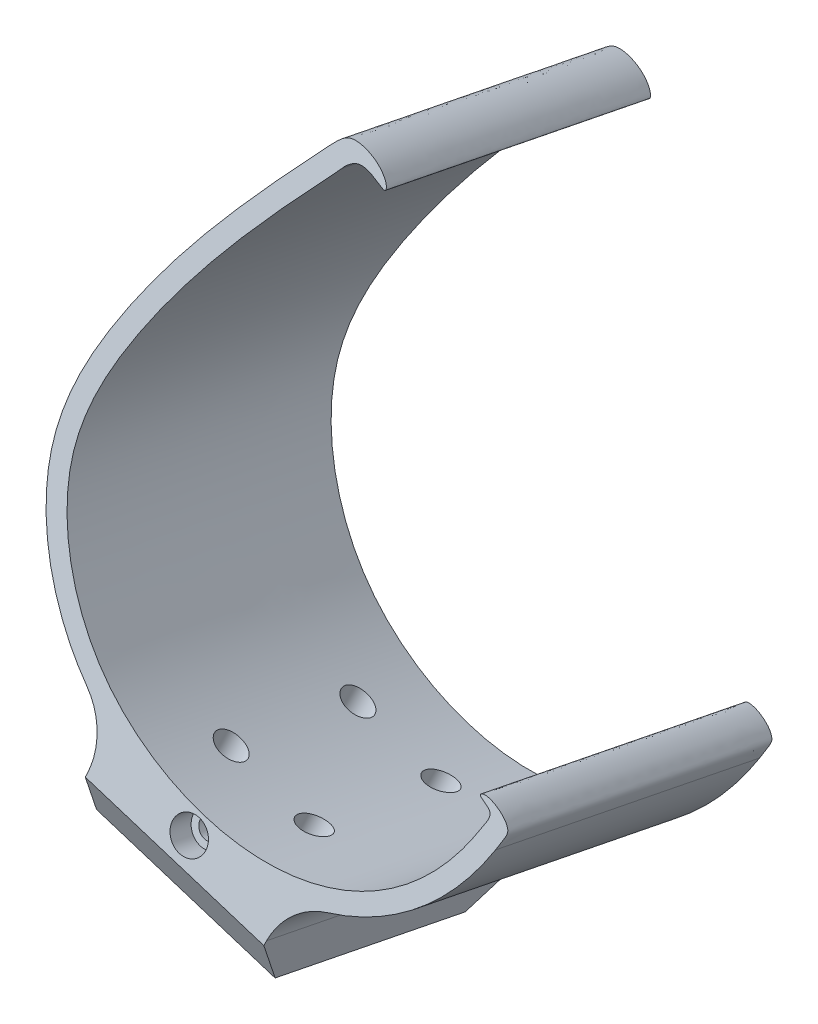
SolidWorks part; units mm, degrees
ref_plane "前视基准面" through (0, 0, 0) normal (0, 0, 1) x (1, 0, 0)
ref_plane "上视基准面" through (0, 0, 0) normal (0, 1, 0) x (1, 0, 0)
ref_plane "右视基准面" through (0, 0, 0) normal (1, 0, 0) x (0, 0, -1)
sketch "草图1" plane through (0, 0, 0) normal (0, 1, 0) x (1, 0, 0)
  line L0 (0, 0) -> (222.6675, 24.1899) construction
ref_axis "基准轴1" through (0, 0, 0) along (0.9942, 0, -0.108)
ref_plane "基准面1" through (0, 0, 0) normal (0.1039, 0.2733, 0.9563) x (0.9942, 0, -0.108)
ref_plane "基准面2" through (-27.5308, -72.4222, -253.4208) normal (0.1039, 0.2733, 0.9563) x (0.9942, 0, -0.108)
ref_plane "基准面3" through (-22.3363, -58.7576, -205.6055) normal (0.1039, 0.2733, 0.9563) x (0.9942, 0, -0.108)
sketch "草图4" plane through (-22.3363, -58.7576, -205.6055) normal (0.1039, 0.2733, 0.9563) x (0.9942, 0, -0.108)
  line L0 (79.3834, 272.9046) -> (87.7225, 282.9708) construction
  line L1 (112.0627, 212.9053) -> (114.7359, 216.8446) construction
  line L4 (72.7448, 201.9475) -> (65.7031, 188.7012) construction
  line L5 (63.4442, 204.3301) -> (58.8289, 191.1127)
  line L6 (58.8289, 191.1127) -> (87.1519, 181.2229)
  line L7 (87.1519, 181.2229) -> (91.7671, 194.4403)
  line L8 (63.4442, 204.3301) -> (91.7671, 194.4403) construction
  spline S0 degree 3 poles (74.1484, 285.7795) (62.3558, 270.526) (54.7252, 258.5634) (45.6973, 233.4784) (51.7656, 214.4469) (67.4034, 198.0106) (93.971, 192.0622) (111.5208, 203.168) (118.5869, 210.5661) knots 0 0 0 0 0.234318 0.358087 0.509491 0.603672 0.801755 1 1 1 1 construction
  spline S1 degree 3 poles (80.2685, 281.8162) (71.5896, 272.3231) (59.2219, 258.506) (48.7238, 233.8174) (55.1501, 216.1242) (76.1264, 195.39) (104.9106, 192.3189) (115.5741, 212.7023) knots 0 0 0 0 0.265723 0.387791 0.533535 0.620247 1 1 1 1
  spline S2 degree 1 poles (78.0544, 283.8404) (118.2323, 211.3117) knots 0 0 1 1 construction
  spline S3 degree 3 poles (78.0544, 283.8404) (76.0071, 281.6011) (71.9277, 277.1174) (65.98, 270.182) (60.3756, 262.8887) (56.1398, 256.3758) (53.0855, 250.8347) (50.3313, 244.9721) (48.396, 238.6424) (48.1555, 231.8719) (49.0953, 225.2064) (52.0966, 217.2396) (56.8755, 210.4059) (61.5005, 205.8314) (66.6095, 201.8113) (73.8305, 197.7463) (82.4871, 195.0178) (88.9761, 194.3497) (92.5861, 194.4576) (95.1064, 194.669) (98.4182, 195.2046) (102.8301, 196.5828) (107.3291, 198.8951) (110.7888, 201.5519) (113.3299, 204.126) (115.1105, 206.2812) (116.4827, 208.2679) (117.5059, 209.9664) (117.9973, 210.8624) (118.2323, 211.3117) knots 0 0 0 0 0.0625 0.125 0.1875 0.25 0.28125 0.3125 0.375 0.40625 0.4375 0.5 0.5625 0.594067 0.625317 0.6875 0.75 0.795464 0.811089 0.818902 0.84375 0.875 0.90625 0.9375 0.953125 0.96875 0.984375 0.992188 1 1 1 1
  spline S4 degree 3 poles (78.0544, 283.8404) (78.5493, 284.2788) (79.7465, 285.9672) (84.171, 285.4659) (87.0038, 282.6592) (86.5692, 281.0147) (82.6684, 284.5477) (80.3993, 282.0436) (80.2685, 281.8162) knots 0 0 0 0 0.185673 0.241813 0.609549 0.679609 0.872351 1 1 1 1
  spline S5 degree 3 poles (118.2323, 211.3117) (118.5521, 211.9528) (119.5354, 213.676) (119.4253, 214.2858) (118.3847, 215.9401) (115.5389, 217.51) (114.3912, 216.6915) (116.5063, 215.881) (116.6361, 214.573) (116.3945, 214.1973) (115.5741, 212.7023) knots 0 0 0 0 0.094761 0.211303 0.266433 0.590925 0.653669 0.831125 0.867976 1 1 1 1
  point P22 (0, 0)
  point P29 (0, 0)
  point P36 (0, 0)
  point P37 (0, 0)
  point P39 (117.9353, 211.3755)
  point P41 (118.2332, 211.3171)
  point P42 (0, 0)
  point P43 (0, 0)
  point P44 (119.1006, 212.9913)
  point P45 (0, 0)
  point P46 (119.1923, 214.6437)
  point P47 (116.7234, 215.4634)
  point P48 (115.5741, 212.7023)
  point P49 (0, 0)
  point P50 (116.7539, 215.361)
  point P51 (116.6714, 215.0743)
  point P52 (116.5779, 215.101)
  dimension "D2" = 8
  dimension "D3" = 6
  dimension "D5" = 30
  dimension "D6" = 30
  dimension "D7" = 90
  dimension "D8" = 90
  dimension "D9" = 14
  dimension "D1" = 3
extrude "凸台-拉伸1" add sketch "草图4" along normal blind 50 contours S3 | S3 S5 S1 S4 region at (46.5567, 125.9212, -265.8671) region at (22.1035, 177.4414, -277.9339)
ref_plane "基准面5" through (60.2199, 182.3792, -58.6621) normal (-0.2999, -0.9082, 0.2921) x (-0.954, 0.2855, -0.0918)
sketch "草图8" plane through (60.2199, 182.3792, -58.6621) normal (-0.2999, -0.9082, 0.2921) x (-0.954, 0.2855, -0.0918)
  line L0 (15.9195, 214.5423) -> (10.4746, 164.8396) construction
  line L1 (30.8303, 212.9088) -> (1.0087, 216.1757) construction
  line L2 (25.3854, 163.2062) -> (-4.4362, 166.4731) construction
  line L3 (14.2915, 199.6812) -> (12.1026, 179.7007)
  arc A0 (14.2915, 199.6812) -> (12.1026, 179.7007) centre (13.197, 189.691) ccw
  dimension "D1" = 20.1
revolve "切除-旋转1" cut sketch "草图8" angle 360 about L0
sketch "草图9" plane through (59.92, 181.4711, -58.37) normal (-0.2999, -0.9082, 0.2921) x (-0.954, 0.2855, -0.0918)
  line L0 (25.3861, 163.2061) -> (30.8312, 212.9087) construction
  line L1 (25.3861, 163.2061) -> (-4.4355, 166.4731) construction
  line L2 (-4.4355, 166.4731) -> (1.0096, 216.1757) construction
  line L3 (30.8312, 212.9087) -> (1.0096, 216.1757) construction
  line L4 (25.3861, 163.2061) -> (30.8312, 212.9087) construction
  circle A0 centre (18.8494, 177) radius 1.65
  circle A1 centre (4.9327, 178.5246) radius 1.65
  circle A2 centre (21.463, 200.8572) radius 1.65
  circle A3 centre (7.5463, 202.3819) radius 1.65
  dimension "D1" = 3.3
  dimension "D2" = 3.3
  dimension "D3" = 3.3
  dimension "D4" = 3.3
  dimension "D10" = 13
  dimension "D5" = 8
  dimension "D6" = 13
  dimension "D7" = 13
  dimension "D8" = 8
  dimension "D9" = 13
  dimension "D11" = 8
  dimension "D12" = 8
extrude "切除-拉伸1" cut sketch "草图9" against normal through all
ref_plane "基准面6" through (62.7687, 190.0986, -61.1451) normal (-0.2999, -0.9082, 0.2921) x (-0.954, 0.2855, -0.0918)
sketch "草图10" plane through (62.7687, 190.0986, -61.1451) normal (-0.2999, -0.9082, 0.2921) x (-0.954, 0.2855, -0.0918)
  circle A0 centre (21.463, 200.8572) radius 2.4
  circle A1 centre (7.5463, 202.3819) radius 2.4
  circle A2 centre (4.9327, 178.5246) radius 2.4
  circle A3 centre (18.8494, 177) radius 2.4
  dimension "D1" = 4.8
  dimension "D2" = 4.8
  dimension "D3" = 4.8
  dimension "D4" = 4.8
extrude "切除-拉伸2" cut sketch "草图10" against normal blind 6.5
fillet "圆角1" radius 10 2 edges at (37.303, 144.6262, -244.065) (65.7522, 135.1129, -244.4369)
chamfer "倒角1" distance 7 angle 45 2 edges at (49.9268, 133.9876, -216.2538) (44.7323, 120.323, -264.069)
sketch "草图12" plane through (-22.3363, -58.7576, -205.6055) normal (-0.1039, -0.2733, -0.9563) x (-0.9946, 0.0285, 0.0999)
  line L1 (-53.1315, 192.7743) -> (-81.7355, 183.7294) construction
  circle A0 centre (-70.7499, 198.74) radius 1.65
  dimension "D1" = 3.3
  dimension "D2" = 11
extrude "切除-拉伸3" cut sketch "草图12" against normal through all
sketch "草图13" plane through (-22.3363, -58.7576, -205.6055) normal (-0.1039, -0.2733, -0.9563) x (-0.9946, 0.0285, 0.0999)
  circle A0 centre (-70.7499, 198.74) radius 2.4
  dimension "D1" = 4.8
extrude "切除-拉伸4" cut sketch "草图13" against normal blind 5.5
sketch "草图14" plane through (-17.1418, -45.0931, -157.7903) normal (0.1039, 0.2733, 0.9563) x (0.9946, -0.0285, -0.0999)
  circle A0 centre (70.7499, 198.74) radius 2.75
  dimension "D1" = 5.5
extrude "切除-拉伸6" cut sketch "草图14" against normal blind 4
equation "\"D9@草图4\"=11+3"
